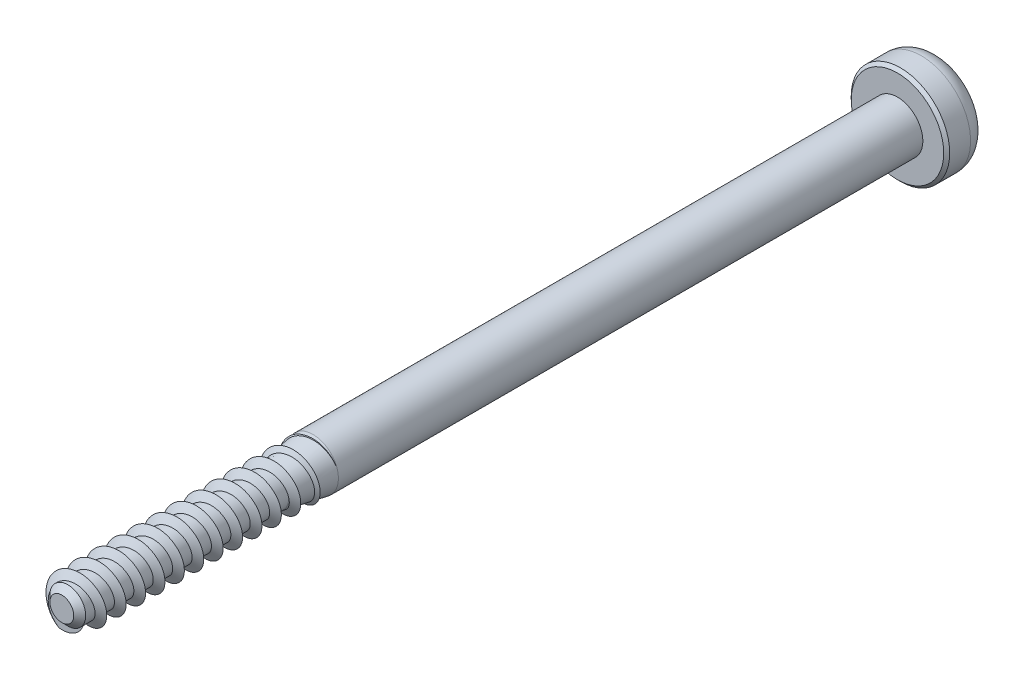
SolidWorks part; units mm, degrees
ref_plane "Front Plane" through (0, 0, 0) normal (0, 0, 1) x (1, 0, 0)
ref_plane "Top Plane" through (0, 0, 0) normal (0, 1, 0) x (1, 0, 0)
ref_plane "Right Plane" through (0, 0, 0) normal (1, 0, 0) x (0, 0, -1)
sketch "Sketch1" plane through (0, 0, 0) normal (1, 0, 0) x (0, 0, -1)
  line L0 (0, 0) -> (-116.6726, 0) construction
  line L1 (-28, 0) -> (-28, 0.6)
  line L2 (-28, 0.6) -> (-21, 0.6)
  line L3 (-21, 0.6) -> (-19.5822, 0.85)
  line L4 (-19.5822, 0.85) -> (0, 0.85)
  line L5 (0, 0.85) -> (0, 1.65)
  line L6 (0, 1.65) -> (0.8, 1.65)
  line L7 (1.4, 1.05) -> (1.4, 0)
  line L8 (1.4, 0) -> (-28, 0)
  arc A0 (1.4, 1.05) -> (0.8, 1.65) centre (0.8, 1.05) ccw
  dimension "D8" = 0.6
  dimension "D1" = 1.7
  dimension "D2" = 1.4
  dimension "D3" = 3.3
  dimension "D4" = 1.2
  dimension "D5" = 28
  dimension "D6" = 10
  dimension "D7" = 7
revolve "Revolve1" add sketch "Sketch1" angle 360 about L0
sketch "Sketch2" plane through (0, 0, 28) normal (0, 0, 1) x (1, 0, 0)
  circle A0 centre (0, 0) radius 0.725
  dimension "D1" = 1.45
curve "Helix/Spiral1" pitch 0.65 height 8.45 radius 0.725 centre (0, 0, 28) axis (0, 0, -1) start towards (1, 0, 0)
sketch "Sketch3" plane through (0, 0, 0) normal (0, 1, 0) x (1, 0, 0)
  line L0 (0.725, -28) -> (1.0309, -28) construction
  line L1 (0.59, -27.8499) -> (0.85, -28)
  line L2 (0.59, -28.1501) -> (0.85, -28)
  line L3 (0.59, -27.8499) -> (0.59, -28.1501)
  line L4 (-0.6, -28) -> (0.6, -28) construction
  line L5 (0, 0) -> (0, -25.3431) construction
  spline S0 degree 3 poles (0.725, -28) (0.725, -27.9865) (0.6869, -27.9591) (0.5241, -27.9184) (0.2808, -27.8775) (-0.0056, -27.8367) (-0.2912, -27.7959) (-0.5321, -27.7551) (-0.6911, -27.7143) (-0.744, -27.6734) (-0.6825, -27.6326) (-0.5161, -27.5918) (-0.2703, -27.551) (0.0169, -27.5101) (0.3016, -27.4693) (0.5399, -27.4285) (0.6952, -27.3877) (0.7437, -27.3469) (0.6779, -27.306) (0.5079, -27.2652) (0.2598, -27.2244) (-0.0282, -27.1836) (-0.3119, -27.1428) (-0.5476, -27.1019) (-0.6992, -27.0611) (-0.7433, -27.0203) (-0.6731, -26.9795) (-0.4995, -26.9386) (-0.2492, -26.8978) (0.0395, -26.857) (0.3221, -26.8162) (0.5552, -26.7754) (0.703, -26.7345) (0.7427, -26.6937) (0.6683, -26.6529) (0.4911, -26.6121) (0.2385, -26.5713) (-0.0508, -26.5304) (-0.3323, -26.4896) (-0.5627, -26.4488) (-0.7066, -26.408) (-0.7419, -26.3671) (-0.6632, -26.3263) (-0.4826, -26.2855) (-0.2278, -26.2447) (0.062, -26.2039) (0.3423, -26.163) (0.57, -26.1222) (0.71, -26.0814) (0.741, -26.0406) (0.658, -25.9998) (0.4739, -25.9589) (0.217, -25.9181) (-0.0733, -25.8773) (-0.3523, -25.8365) (-0.5772, -25.7957) (-0.7133, -25.7548) (-0.7399, -25.714) (-0.6527, -25.6732) (-0.4652, -25.6324) (-0.2062, -25.5915) (0.0845, -25.5507) (0.3622, -25.5099) (0.5842, -25.4691) (0.7165, -25.4283) (0.7386, -25.3874) (0.6472, -25.3466) (0.4563, -25.3058) (0.1953, -25.265) (-0.0957, -25.2242) (-0.372, -25.1833) (-0.5912, -25.1425) (-0.7194, -25.1017) (-0.7371, -25.0609) (-0.6415, -25.02) (-0.4473, -24.9792) (-0.1844, -24.9384) (0.1069, -24.8976) (0.3818, -24.8568) (0.5979, -24.8159) (0.7222, -24.7751) (0.7355, -24.7343) (0.6357, -24.6935) (0.4383, -24.6527) (0.1734, -24.6118) (-0.1181, -24.571) (-0.3914, -24.5302) (-0.6046, -24.4894) (-0.7249, -24.4486) (-0.7337, -24.4077) (-0.6298, -24.3669) (-0.4291, -24.3261) (-0.1624, -24.2853) (0.1292, -24.2444) (0.401, -24.2036) (0.6111, -24.1628) (0.7273, -24.122) (0.7318, -24.0812) (0.6237, -24.0403) (0.4198, -23.9995) (0.1514, -23.9587) (-0.1403, -23.9179) (-0.4104, -23.8771) (-0.6175, -23.8362) (-0.7296, -23.7954) (-0.7296, -23.7546) (-0.6175, -23.7138) (-0.4104, -23.6729) (-0.1403, -23.6321) (0.1514, -23.5913) (0.4198, -23.5505) (0.6237, -23.5097) (0.7318, -23.4688) (0.7273, -23.428) (0.6111, -23.3872) (0.401, -23.3464) (0.1292, -23.3056) (-0.1624, -23.2647) (-0.4291, -23.2239) (-0.6298, -23.1831) (-0.7337, -23.1423) (-0.7249, -23.1014) (-0.6046, -23.0606) (-0.3914, -23.0198) (-0.1181, -22.979) (0.1734, -22.9382) (0.4383, -22.8973) (0.6357, -22.8565) (0.7355, -22.8157) (0.7222, -22.7749) (0.5979, -22.7341) (0.3818, -22.6932) (0.1069, -22.6524) (-0.1844, -22.6116) (-0.4473, -22.5708) (-0.6415, -22.53) (-0.7371, -22.4891) (-0.7194, -22.4483) (-0.5912, -22.4075) (-0.372, -22.3667) (-0.0957, -22.3258) (0.1953, -22.285) (0.4563, -22.2442) (0.6472, -22.2034) (0.7386, -22.1626) (0.7165, -22.1217) (0.5842, -22.0809) (0.3622, -22.0401) (0.0845, -21.9993) (-0.2062, -21.9585) (-0.4652, -21.9176) (-0.6527, -21.8768) (-0.7399, -21.836) (-0.7133, -21.7952) (-0.5772, -21.7543) (-0.3523, -21.7135) (-0.0733, -21.6727) (0.217, -21.6319) (0.4739, -21.5911) (0.658, -21.5502) (0.741, -21.5094) (0.71, -21.4686) (0.57, -21.4278) (0.3423, -21.387) (0.062, -21.3461) (-0.2278, -21.3053) (-0.4826, -21.2645) (-0.6632, -21.2237) (-0.7419, -21.1829) (-0.7066, -21.142) (-0.5627, -21.1012) (-0.3323, -21.0604) (-0.0508, -21.0196) (0.2385, -20.9787) (0.4911, -20.9379) (0.6683, -20.8971) (0.7427, -20.8563) (0.703, -20.8155) (0.5552, -20.7746) (0.3221, -20.7338) (0.0395, -20.693) (-0.2492, -20.6522) (-0.4995, -20.6114) (-0.6731, -20.5705) (-0.7433, -20.5297) (-0.6992, -20.4889) (-0.5476, -20.4481) (-0.3119, -20.4072) (-0.0282, -20.3664) (0.2598, -20.3256) (0.5079, -20.2848) (0.6779, -20.244) (0.7437, -20.2031) (0.6952, -20.1623) (0.5399, -20.1215) (0.3016, -20.0807) (0.0169, -20.0399) (-0.2703, -19.999) (-0.5161, -19.9582) (-0.6825, -19.9174) (-0.744, -19.8766) (-0.6911, -19.8357) (-0.5321, -19.7949) (-0.2912, -19.7541) (-0.0056, -19.7133) (0.2808, -19.6725) (0.5241, -19.6316) (0.6869, -19.5909) (0.725, -19.5635) (0.725, -19.55) knots 0 0 0 0 0.004831 0.009662 0.014493 0.019324 0.024155 0.028986 0.033816 0.038647 0.043478 0.048309 0.05314 0.057971 0.062802 0.067633 0.072464 0.077295 0.082126 0.086957 0.091787 0.096618 0.101449 0.10628 0.111111 0.115942 0.120773 0.125604 0.130435 0.135266 0.140097 0.144928 0.149758 0.154589 0.15942 0.164251 0.169082 0.173913 0.178744 0.183575 0.188406 0.193237 0.198068 0.202899 0.207729 0.21256 0.217391 0.222222 0.227053 0.231884 0.236715 0.241546 0.246377 0.251208 0.256039 0.26087 0.2657 0.270531 0.275362 0.280193 0.285024 0.289855 0.294686 0.299517 0.304348 0.309179 0.31401 0.318841 0.323671 0.328502 0.333333 0.338164 0.342995 0.347826 0.352657 0.357488 0.362319 0.36715 0.371981 0.376812 0.381643 0.386473 0.391304 0.396135 0.400966 0.405797 0.410628 0.415459 0.42029 0.425121 0.429952 0.434783 0.439614 0.444444 0.449275 0.454106 0.458937 0.463768 0.468599 0.47343 0.478261 0.483092 0.487923 0.492754 0.497585 0.502415 0.507246 0.512077 0.516908 0.521739 0.52657 0.531401 0.536232 0.541063 0.545894 0.550725 0.555556 0.560386 0.565217 0.570048 0.574879 0.57971 0.584541 0.589372 0.594203 0.599034 0.603865 0.608696 0.613527 0.618357 0.623188 0.628019 0.63285 0.637681 0.642512 0.647343 0.652174 0.657005 0.661836 0.666667 0.671498 0.676329 0.681159 0.68599 0.690821 0.695652 0.700483 0.705314 0.710145 0.714976 0.719807 0.724638 0.729469 0.7343 0.73913 0.743961 0.748792 0.753623 0.758454 0.763285 0.768116 0.772947 0.777778 0.782609 0.78744 0.792271 0.797101 0.801932 0.806763 0.811594 0.816425 0.821256 0.826087 0.830918 0.835749 0.84058 0.845411 0.850242 0.855072 0.859903 0.864734 0.869565 0.874396 0.879227 0.884058 0.888889 0.89372 0.898551 0.903382 0.908213 0.913043 0.917874 0.922705 0.927536 0.932367 0.937198 0.942029 0.94686 0.951691 0.956522 0.961353 0.966184 0.971014 0.975845 0.980676 0.985507 0.990338 0.995169 1 1 1 1 construction
  dimension "D1" = 60
  dimension "D2" = 1.7
  dimension "D3" = 0.26
sweep "Sweep1" add profiles "Sketch3" path "Helix/Spiral1"
sketch "Sketch4" plane through (0, 0, 0) normal (0, 1, 0) x (1, 0, 0)
  line L0 (0, 0) -> (0, -26.2458) construction
  line L1 (0.4, -28) -> (0.6, -27.8)
  line L2 (-0.6, -28) -> (0.6, -28) construction
  line L3 (0.6, -27.8557) -> (0.6, -27.4943) construction
  line L4 (0.6, -27.8) -> (1.0924, -27.8)
  line L5 (1.0924, -27.8) -> (1.0924, -28.3)
  line L6 (1.0924, -28.3) -> (0.4, -28.3)
  line L7 (0.4, -28.3) -> (0.4, -28)
  line L8 (0.6, -27.8557) -> (0.6, -28) construction
  line L9 (0.0675, -28) -> (0.59, -28) construction
  dimension "D1" = 0.2
  dimension "D2" = 0.2
  dimension "D3" = 0.5
revolve "Cut-Revolve1" cut sketch "Sketch4" angle 360 about L0
chamfer "Chamfer1" distance 0.1 angle 45 1 edges at (-1.65, 0, 0)
sketch "Sketch5" plane through (0, 0, -1.4) normal (0, 0, -1) x (-1, 0, 0)
  line L0 (-0.35, 0.35) -> (-1.15, 0.35)
  line L1 (0.35, -1.15) -> (-0.35, -1.15)
  line L2 (0.35, -1.15) -> (0.35, -0.35)
  line L3 (0.35, 1.15) -> (-0.35, 1.15)
  line L4 (-0.35, -1.15) -> (-0.35, -0.35)
  line L5 (0.35, -1.15) -> (-0.35, 1.15) construction
  line L6 (0.35, 1.15) -> (-0.35, -1.15) construction
  line L7 (1.15, -0.35) -> (0.35, -0.35)
  line L8 (1.15, -0.35) -> (1.15, 0.35)
  line L9 (1.15, 0.35) -> (0.35, 0.35)
  line L10 (-1.15, -0.35) -> (-1.15, 0.35)
  line L11 (1.15, -0.35) -> (-1.15, 0.35) construction
  line L12 (1.15, 0.35) -> (-1.15, -0.35) construction
  line L13 (-0.35, 0.35) -> (-0.35, 1.15)
  line L14 (-0.35, -0.35) -> (-1.15, -0.35)
  line L15 (0.35, 0.35) -> (0.35, 1.15)
  point P0 (0, 0)
  point P6 (0, 0)
  dimension "D1" = 0.7
  dimension "D2" = 2.3
  dimension "D3" = 2.3
extrude "Cut-Extrude1" cut sketch "Sketch5" against normal blind 1 draft 15
